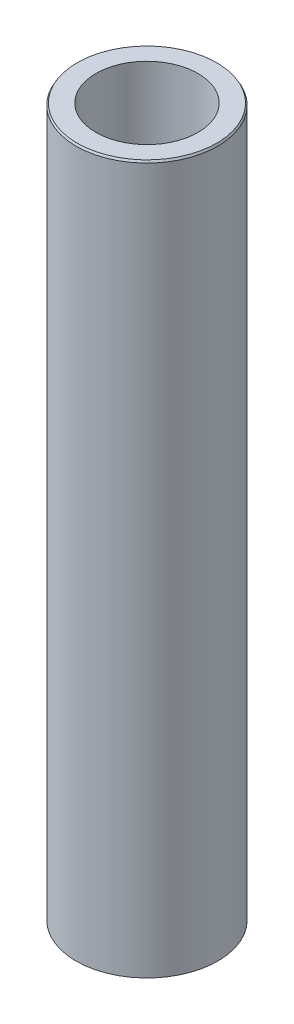
SolidWorks part; units mm, degrees
ref_plane "Front Plane" through (0, 0, 0) normal (0, 0, 1) x (1, 0, 0)
ref_plane "Top Plane" through (0, 0, 0) normal (0, 1, 0) x (1, 0, 0)
ref_plane "Right Plane" through (0, 0, 0) normal (1, 0, 0) x (0, 0, -1)
sketch "Sketch1" plane through (0, 0, 0) normal (0, 1, 0) x (1, 0, 0)
  circle A0 centre (0, 0) radius 60
  dimension "SHAFT_OD" = 120
extrude "Boss-Extrude1" add sketch "Sketch1" along normal blind 600
sketch "Sketch2" plane through (0, 0, 0) normal (0, 1, 0) x (1, 0, 0)
  circle A0 centre (0, 0) radius 43.2394
  dimension "BORE_D" = 86.4788
extrude "Cut-Extrude1" cut sketch "Sketch2" along normal through all
chamfer "Chamfer1" distance 1.6749 angle 30 2 edges at (0, 600, 60) (0, 0, 60) first distance on face at (0, 600, 60) first distance on face at (0, 0, 43.2394)
